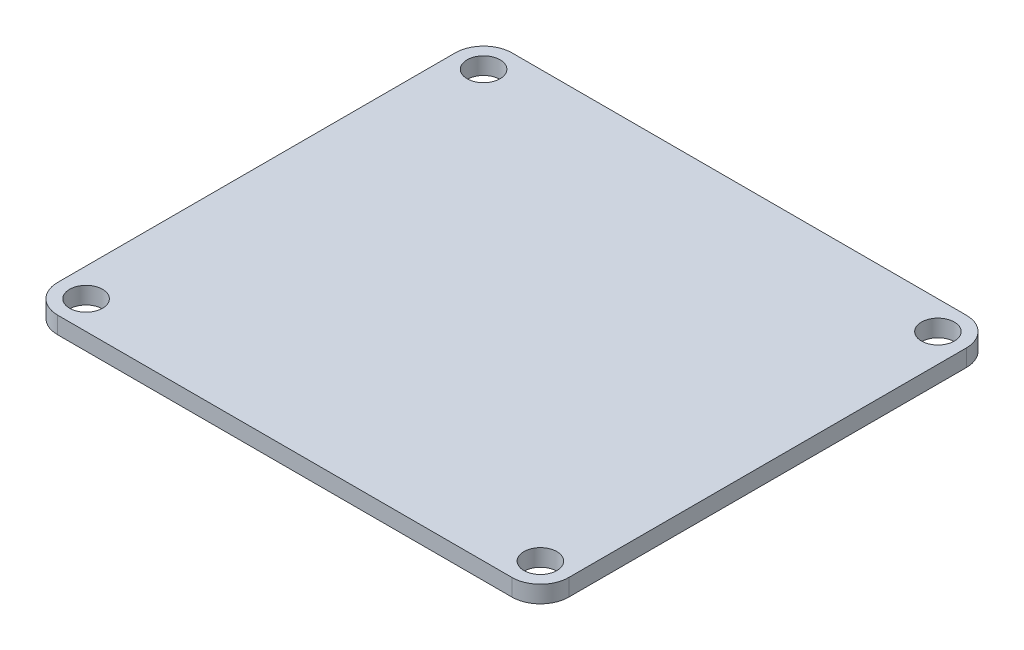
SolidWorks part; units mm, degrees
ref_plane "Front Plane" through (0, 0, 0) normal (0, 0, 1) x (1, 0, 0)
ref_plane "Top Plane" through (0, 0, 0) normal (0, 1, 0) x (1, 0, 0)
ref_plane "Right Plane" through (0, 0, 0) normal (1, 0, 0) x (0, 0, -1)
sketch "Sketch1" plane through (0, 0, 0) normal (0, 1, 0) x (1, 0, 0)
  line L1 (-22.86, 20.32) -> (22.86, 20.32)
  line L2 (-22.86, 20.32) -> (-22.86, -20.32)
  line L3 (-22.86, -20.32) -> (22.86, -20.32)
  line L4 (22.86, 20.32) -> (22.86, -20.32)
  line L5 (-22.86, 20.32) -> (22.86, -20.32) construction
  line L6 (-22.86, -20.32) -> (22.86, 20.32) construction
  point P0 (0, 0)
  dimension "D1" = 40.64
  dimension "D2" = 45.72
extrude "Boss-Extrude1" add sketch "Sketch1" along normal mid plane 1.524
fillet "Fillet1" radius 2.54 4 edges at (22.86, 0, -20.32) (-22.86, 0, -20.32) (22.86, 0, 20.32) (-22.86, 0, 20.32)
hole_wizard "#4 Clearance Hole1" positions "Sketch2" profile "Sketch3" hole size "#4" standard "ANSI Inch" end condition through all
sketch "Sketch2" plane through (0, 0.762, 0) normal (0, 1, 0) x (1, 0, 0)
  line L1 (-20.32, -17.78) -> (20.32, -17.78)
  line L2 (-20.32, -17.78) -> (-20.32, 17.78)
  line L3 (-20.32, 17.78) -> (20.32, 17.78)
  line L4 (20.32, -17.78) -> (20.32, 17.78)
  line L5 (-20.32, -17.78) -> (20.32, 17.78) construction
  line L6 (-20.32, 17.78) -> (20.32, -17.78) construction
  point P2 (20.32, 17.78)
  point P63 (-20.32, -17.78)
  point P64 (-20.32, 17.78)
  point P65 (20.32, -17.78)
  dimension "D1" = 35.56
  dimension "D2" = 40.64
sketch "Sketch3" plane through (20.32, 0.762, -17.78) normal (1, 0, 0) x (0, 0, 1)
  line L0 (0, 0) -> (0, 1.524)
  line L1 (0, 1.524) -> (1.4732, 1.524)
  line L2 (1.4732, 1.524) -> (1.4732, 0)
  line L5 (1.4732, 0) -> (0, 0)
  line L11 (0, -6.35) -> (0, 107.95) construction
  dimension "Thru Hole Dia." = 2.9464
  dimension "Thru Hole Depth" = 1.524
